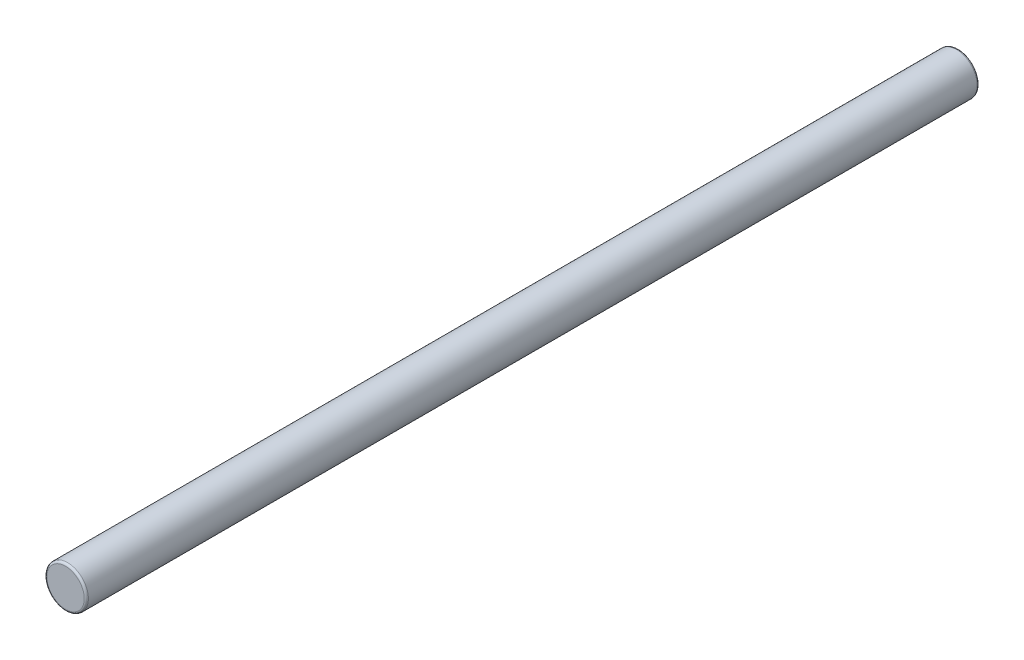
SolidWorks part; units mm, degrees
ref_plane "Front Plane" through (0, 0, 0) normal (0, 0, 1) x (1, 0, 0)
ref_plane "Top Plane" through (0, 0, 0) normal (0, 1, 0) x (1, 0, 0)
ref_plane "Right Plane" through (0, 0, 0) normal (1, 0, 0) x (0, 0, -1)
sketch "Sketch1" plane through (0, 0, 0) normal (0, 0, 1) x (1, 0, 0)
  circle A0 centre (0, 0) radius 0.5
  dimension "D1" = 1
extrude "Boss-Extrude1" add sketch "Sketch1" along normal mid plane 4
sketch "Sketch2" plane through (0, 0, 2) normal (0, 0, 1) x (1, 0, 0)
  circle A0 centre (0, 0) radius 0.75
  dimension "D1" = 1.5
extrude "Boss-Extrude2" add sketch "Sketch2" along normal blind 8
sketch "Sketch3" plane through (0, 0, -2) normal (0, 0, -1) x (-1, 0, 0)
  circle A0 centre (0, 0) radius 0.75
  dimension "D1" = 1.5
extrude "Boss-Extrude3" add sketch "Sketch3" along normal blind 8
sketch "Sketch4" plane through (0, 0, -10) normal (0, 0, -1) x (-1, 0, 0)
  circle A0 centre (0, 0) radius 0.5
  dimension "D1" = 1
extrude "Boss-Extrude4" add sketch "Sketch4" along normal blind 2 and the other way blind 24
sketch "Sketch5" plane through (0, 0, 2) normal (0, 0, -1) x (-1, 0, 0)
  circle A0 centre (0, 0) radius 0.5
  circle A1 centre (0, 0) radius 1.0832
extrude "Cut-Extrude1" cut sketch "Sketch5" against normal mid plane 40
sketch "Sketch6" plane through (0, 0, -12) normal (0, 0, -1) x (-1, 0, 0)
  circle A0 centre (0, 0) radius 0.9931
extrude "Cut-Extrude2" cut sketch "Sketch6" against normal blind 4.5
fillet "Fillet1" radius 0.05 2 edges at (-0.5, 0, 14) (-0.5, 0, -7.5)
